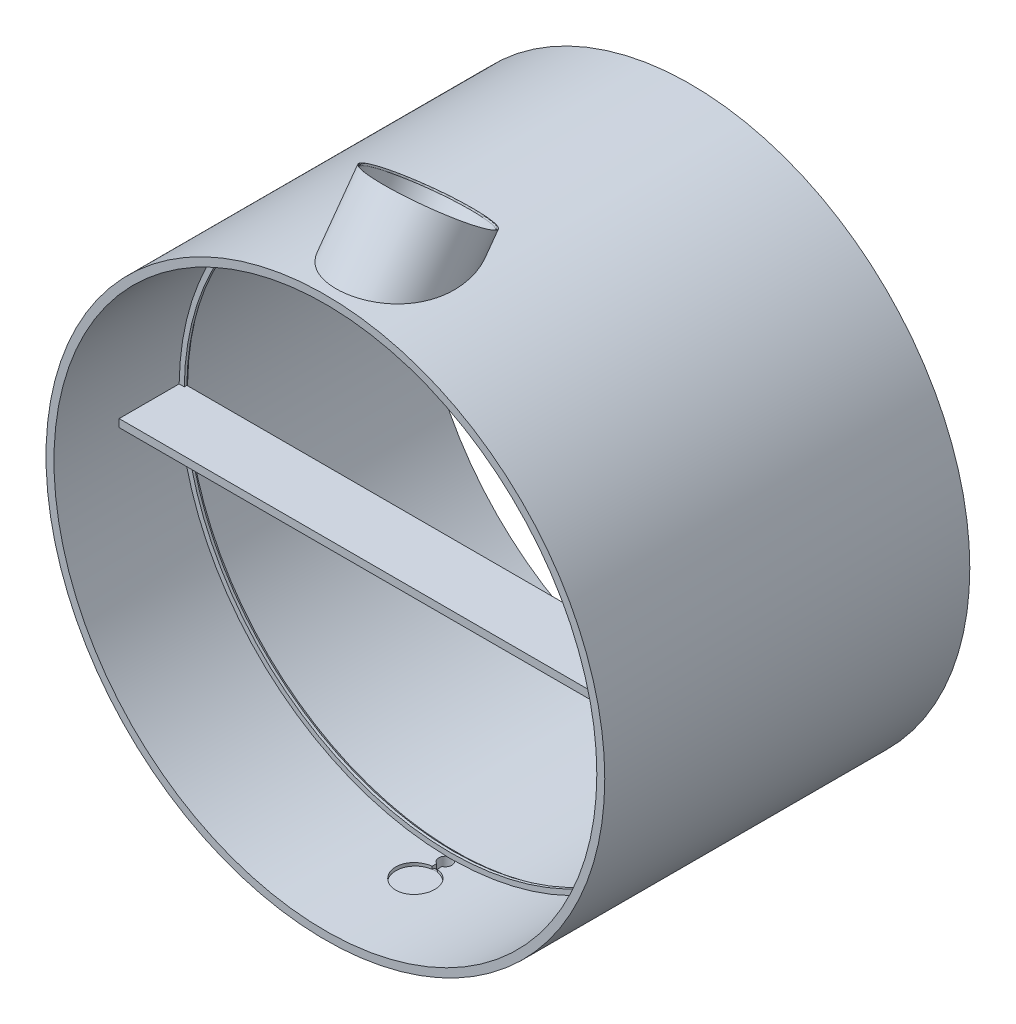
SolidWorks part; units mm, degrees
ref_plane "Front Plane" through (0, 0, 0) normal (0, 0, 1) x (1, 0, 0)
ref_plane "Top Plane" through (0, 0, 0) normal (0, 1, 0) x (1, 0, 0)
ref_plane "Right Plane" through (0, 0, 0) normal (1, 0, 0) x (0, 0, -1)
sketch "Sketch2" plane through (0, 0, 0) normal (0, 0, 1) x (1, 0, 0)
  circle A0 centre (0, 0) radius 107.15
  dimension "D1" = 214.3
extrude "Boss-Extrude2" add sketch "Sketch2" along normal blind 70 and the other way blind 70
sketch "Sketch3" plane through (0, 0, 70) normal (0, 0, 1) x (1, 0, 0)
  circle A0 centre (0, 0) radius 105.65
  dimension "D1" = 211.3
ref_plane "Plane2" through (0, 0, 45) normal (0, 0, 1) x (1, 0, 0)
ref_plane "Plane3" through (0, 107.15, 0) normal (0, 1, 0) x (1, 0, 0)
sketch "Sketch8" plane through (0, 107.15, 0) normal (0, 1, 0) x (1, 0, 0)
  line L0 (0, 70) -> (0, -40)
  line L1 (107.15, 70) -> (-107.15, 70) construction
  line L2 (0, -181.6691) -> (0, 181.6691) construction
  dimension "D1" = 110
ref_plane "Plane4" through (0, 107.15, 40) normal (0, 0, 1) x (1, 0, 0)
ref_axis "Axis1" through (60.5, 107.15, 40) along (-1, 0, 0)
ref_plane "Plane5" through (0, 51.1095, -37.1332) normal (0, -0.809, 0.5878) x (1, 0, 0)
sketch "Sketch10" plane through (0, 51.1095, -37.1332) normal (0, -0.809, 0.5878) x (1, 0, 0)
  circle A0 centre (0, 95.3419) radius 19
  dimension "D1" = 38
extrude "Cut-Extrude2" cut sketch "Sketch10" along normal mid plane 20
ref_plane "Plane6" through (0, 63.2447, -45.95) normal (0, -0.809, 0.5878) x (1, 0, 0)
ref_axis "Axis2" through (0, 49.8364, 81.6408) along (0, 0.809, -0.5878)
sketch "Sketch16" plane through (0, 63.2447, -45.95) normal (0, -0.809, 0.5878) x (1, 0, 0)
  circle A0 centre (0, 95.3419) radius 20
  dimension "D1" = 40
sketch "Sketch18" plane through (0, 63.2447, -45.95) normal (0, -0.809, 0.5878) x (1, 0, 0)
  line L0 (0, -181.6691) -> (0, 181.6691) construction
  circle A0 centre (0, 95.3419) radius 21
  dimension "D1" = 42
extrude "Boss-Extrude6" add sketch "Sketch18" along normal blind 32 and the other way blind 1
sketch "Sketch22" plane through (0, 63.2447, -45.95) normal (0, -0.809, 0.5878) x (1, 0, 0)
  line L0 (0, -181.6691) -> (0, 181.6691) construction
  circle A0 centre (0, 95.3419) radius 19
  dimension "D1" = 38
sketch "Sketch26" plane through (0, 51.1095, -37.1332) normal (0, -0.809, 0.5878) x (1, 0, 0)
  circle A0 centre (0, 95.3419) radius 19
ref_axis "Axis3" through (0, 117.1821, 32.7112) along (0, -0.809, 0.5878)
ref_plane "Plane7" through (0, 0, 0) normal (-1, 0, 0) x (0, 0, 1)
sketch "Sketch27" plane through (0, 0, 0) normal (-1, 0, 0) x (0, 0, 1)
  line L0 (40, 107.15) -> (276.5347, 1.838)
  line L1 (-70, 107.15) -> (40, 107.15) construction
  line L2 (40, 107.15) -> (63.2582, -114.1368)
  line L3 (78.2472, 54.5072) -> (-16.3702, 184.7369) construction
  dimension "D1" = 30
  dimension "D2" = 30
sketch "Sketch31" plane through (0, 0, 0) normal (-1, 0, 0) x (0, 0, 1)
  line L0 (40, 107.15) -> (205.9898, -4.8115)
  line L1 (40, 107.15) -> (93.2086, -78.4105)
  line L2 (78.2472, 54.5072) -> (-16.3702, 184.7369) construction
  dimension "D1" = 20
  dimension "D2" = 20
ref_plane "Plane8" through (0, -107.15, 0) normal (0, 1, 0) x (1, 0, 0)
ref_plane "Plane9" through (0, 0, 70) normal (0, 0, 1) x (1, 0, 0)
ref_plane "Plane10" through (0, 0, -70) normal (0, 0, -1) x (-1, 0, 0)
sketch "Sketch39" plane through (0, -107.15, 0) normal (0, 1, 0) x (1, 0, 0)
  line L0 (0, 70) -> (0, -24)
  line L1 (0, 115.5498) -> (0, -115.5498) construction
  line L2 (0, -78.2472) -> (0, 16.3702) construction
  dimension "D1" = 94
ref_plane "Plane12" through (0, 0, 35.5) normal (0, 0, 1) x (1, 0, 0)
ref_plane "Plane13" through (0, -105.15, 0) normal (0, 1, 0) x (1, 0, 0)
ref_axis "Axis5" through (0, 116.215, 35.5) along (0, -1, 0)
sketch "Sketch54" plane through (0, -107.15, 0) normal (0, 1, 0) x (1, 0, 0)
  line L0 (0, 70) -> (0, 1.5)
  dimension "D1" = 68.5
sketch "Sketch56" plane through (0, -107.15, 0) normal (0, 1, 0) x (1, 0, 0)
  line L0 (0, -181.6691) -> (0, 181.6691) construction
  circle A0 centre (0, 1.5) radius 30.95
  dimension "D1" = 61.9
extrude "Boss-Extrude7" add sketch "Sketch56" along normal blind 5 and the other way blind 6
sketch "Sketch20" plane through (0, 0, 70) normal (0, 0, 1) x (1, 0, 0)
  circle A0 centre (0, 0) radius 104.1
  dimension "D1" = 208.2
extrude "Cut-Extrude3" cut sketch "Sketch20" against normal blind 140
sketch "Sketch51" plane through (0, -107.15, 0) normal (0, 1, 0) x (1, 0, 0)
  circle A0 centre (0, -24) radius 2.5
  dimension "D1" = 5
extrude "Cut-Extrude14" cut sketch "Sketch51" against normal blind 55 and the other way blind 5
sketch "Sketch58" plane through (0, -105.15, 0) normal (0, 1, 0) x (1, 0, 0)
  line L0 (0, -24) -> (1, -24)
  line L1 (1, -24) -> (1, -34.1928)
  line L2 (1, -34.1928) -> (-1, -34.1928)
  line L3 (-1, -34.1928) -> (-1, -24)
  line L4 (-1, -24) -> (0, -24)
  dimension "D1" = 1
  dimension "D2" = 1
  dimension "D3" = 2
extrude "Cut-Extrude15" cut sketch "Sketch58" along normal blind 5
sketch "Sketch44" plane through (0, -105.15, 0) normal (0, 1, 0) x (1, 0, 0)
  line L0 (0, -181.6691) -> (0, 181.6691) construction
  circle A0 centre (0, -35.5) radius 7.5
  dimension "D1" = 15
extrude "Cut-Extrude10" cut sketch "Sketch44" along normal blind 10
fillet "Fillet3" radius 1.5 1 edges at (0, -105.15, 26.5)
ref_plane "Plane14" through (0, 0, 22) normal (0, 0, 1) x (1, 0, 0)
ref_axis "Axis6" through (0, 0, -70) along (0, 0, 1)
sketch "Sketch61" plane through (0, 0, 22) normal (0, 0, 1) x (1, 0, 0)
  circle A0 centre (0, 0) radius 104.15
  dimension "D1" = 208.3
extrude "Boss-Extrude8" add sketch "Sketch61" against normal blind 2
sketch "Sketch62" plane through (0, 0, 22) normal (0, 0, 1) x (1, 0, 0)
  circle A0 centre (0, 0) radius 102.15
  dimension "D1" = 204.3
extrude "Cut-Extrude16" cut sketch "Sketch62" against normal blind 10
chamfer "Chamfer7" distance 1 angle 35 1 edges at (102.15, 0, 20) first distance on face at (102.15, 0, 22)
sketch "Sketch5" plane through (0, 0, 45) normal (0, 0, 1) x (1, 0, 0)
  line L1 (-105.65, -1.5) -> (105.65, -1.5)
  line L2 (-105.65, -1.5) -> (-105.65, 1.5)
  line L3 (-105.65, 1.5) -> (105.65, 1.5)
  line L4 (105.65, -1.5) -> (105.65, 1.5)
  line L5 (-105.65, -1.5) -> (105.65, 1.5) construction
  line L6 (-105.65, 1.5) -> (105.65, -1.5) construction
  point P0 (0, 0)
  dimension "D1" = 211.3
  dimension "D2" = 3
extrude "Boss-Extrude3" add sketch "Sketch5" against normal blind 24
sketch "Sketch24" plane through (0, 63.2447, -45.95) normal (0, -0.809, 0.5878) x (1, 0, 0)
  line L0 (0, -181.6691) -> (0, 181.6691) construction
  circle A0 centre (0, 95.3419) radius 19.45
  dimension "D1" = 38.9
extrude "Cut-Extrude6" cut sketch "Sketch24" along normal blind 50
sketch "Sketch23" plane through (0, 63.2447, -45.95) normal (0, -0.809, 0.5878) x (1, 0, 0)
  line L1 (0, -181.6691) -> (0, 181.6691) construction
  circle A0 centre (0, 95.3419) radius 20.45
  dimension "D1" = 40.9
extrude "Cut-Extrude5" cut sketch "Sketch23" along normal blind 7 and the other way blind 5
ref_plane "Plane15" through (0, -167.15, 0) normal (0, 1, 0) x (1, 0, 0)
chamfer "Chamfer1" distance 0.5 angle 45 1 edges at (0, -113.15, 29.45)
fillet "Fillet4" radius 0.6 1 edges at (0, 108.0741, 14.051)
ref_axis "Axis7" through (0, 0, -119.9757) along (0, 0, 1)
ref_plane "Plane16" through (0, 0, 0) normal (0, -1, 0) x (-1, 0, 0)
